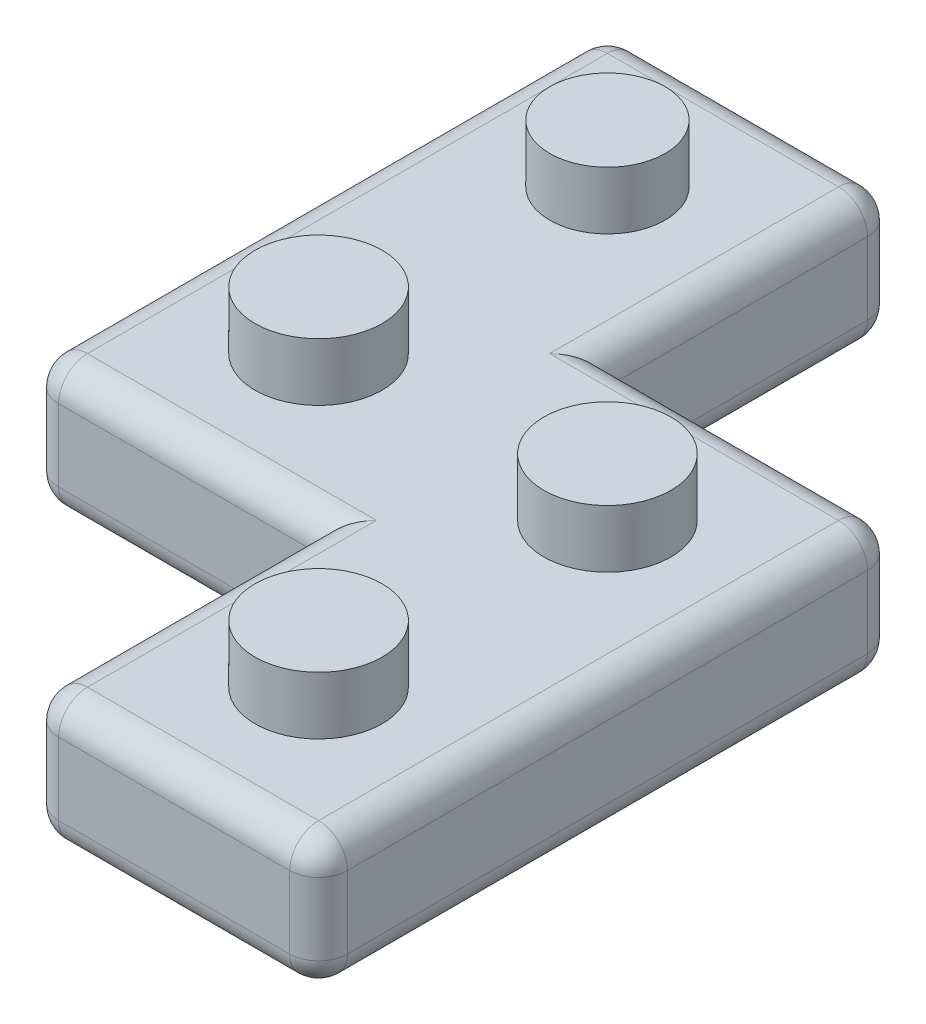
SolidWorks part; units mm, degrees
material "ABS PC"
ref_plane "Front Plane" through (0, 0, 0) normal (0, 0, 1) x (1, 0, 0)
ref_plane "Top Plane" through (0, 0, 0) normal (0, 1, 0) x (1, 0, 0)
ref_plane "Right Plane" through (0, 0, 0) normal (1, 0, 0) x (0, 0, -1)
sketch "Sketch1" plane through (0, 0, 0) normal (0, 1, 0) x (1, 0, 0)
  line L0 (-5.6746, 20.3112) -> (7.0254, 20.3112)
  line L1 (7.0254, 20.3112) -> (7.0254, 7.6112)
  line L2 (7.0254, 7.6112) -> (19.7254, 7.6112)
  line L3 (19.7254, 7.6112) -> (19.7254, -17.7888)
  line L4 (19.7254, -17.7888) -> (7.0254, -17.7888)
  line L5 (7.0254, -17.7888) -> (7.0254, -5.0888)
  line L6 (7.0254, -5.0888) -> (-5.6746, -5.0888)
  line L7 (-5.6746, -5.0888) -> (-5.6746, 20.3112)
  dimension "D1" = 38.1
  dimension "D2" = 12.7
  dimension "D3" = 12.7
  dimension "D4" = 12.7
  dimension "D5" = 12.7
extrude "Boss-Extrude1" add sketch "Sketch1" along normal blind 5.715
sketch "Sketch2" plane through (0, 5.715, 0) normal (0, 1, 0) x (1, 0, 0)
  line L0 (-5.6746, 20.3112) -> (-5.6746, -5.0888) construction
  line L1 (19.7254, -17.7888) -> (19.7254, 7.6112) construction
  line L2 (7.0254, 20.3112) -> (-5.6746, 20.3112) construction
  circle A0 centre (0.6754, 1.2612) radius 2.794
  circle A1 centre (13.3754, 1.2612) radius 2.794
  circle A2 centre (0.6754, 13.9612) radius 2.54
  circle A3 centre (13.3754, -11.4388) radius 2.794
  dimension "D2" = 6.35
  dimension "D4" = 6.35
  dimension "D5" = 12.7
  dimension "D3" = 6.35
  dimension "D6" = 12.7
  dimension "D1" = 2
extrude "Boss-Extrude3" add sketch "Sketch2" along normal blind 2.54
fillet "Fillet1" radius 1.27 21 edges at (19.7254, 2.8575, 17.7888) (7.0254, 0, -13.9612) (0.6754, 0, 5.0888) (13.3754, 0, 17.7888) (19.7254, 0, 5.0888) (7.0254, 5.715, -13.9612) (7.0254, 2.8575, -20.3112) (0.6754, 0, -20.3112) (0.6754, 5.715, -20.3112) (-5.6746, 2.8575, -20.3112) (-5.6746, 5.715, -7.6112) (-5.6746, 2.8575, 5.0888) (0.6754, 5.715, 5.0888) (7.0254, 0, 11.4388) (7.0254, 2.8575, 17.7888) (7.0254, 5.715, 11.4388) (13.3754, 5.715, 17.7888) (19.7254, 5.715, 5.0888) (13.3754, 5.715, -7.6112) (13.3754, 0, -7.6112) (19.7254, 2.8575, -7.6112)
fillet "Fillet2" radius 1.27 3 edges at (-5.3026, 0.372, -19.9392) (-5.3026, 0.372, 4.7168) (-5.6746, 0, -7.6112)
